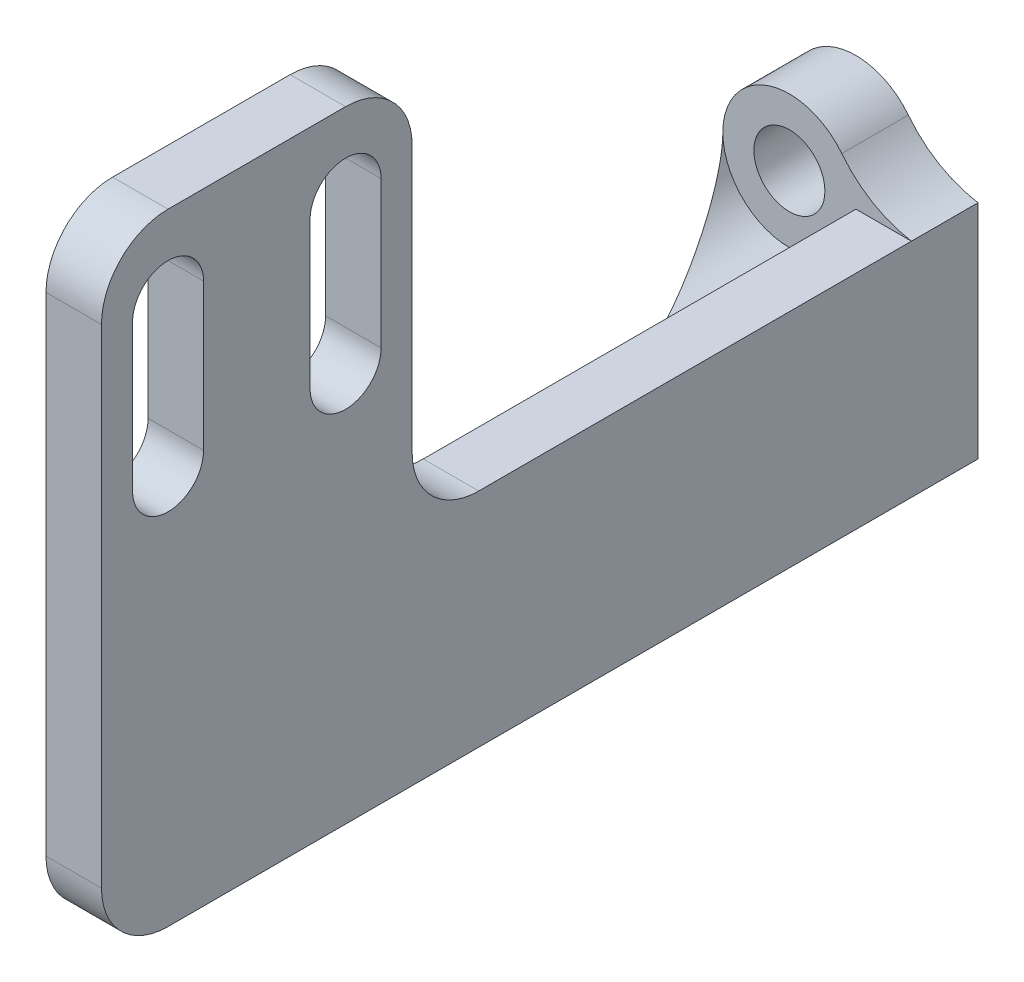
SolidWorks part; units mm, degrees
ref_plane "Front Plane" through (0, 0, 0) normal (0, 0, 1) x (1, 0, 0)
ref_plane "Top Plane" through (0, 0, 0) normal (0, 1, 0) x (1, 0, 0)
ref_plane "Right Plane" through (0, 0, 0) normal (1, 0, 0) x (0, 0, -1)
other "Configuration Table"
sketch "草图1" plane through (0, 0, 0) normal (0, 0, 1) x (1, 0, 0)
  line L0 (-3, -33.0103) -> (-3, -43.0103)
  line L1 (3, -33.0103) -> (3, -43.0103)
  line L3 (3, -33.0103) -> (5.5, -33.0103)
  line L4 (5.5, -33.0103) -> (5.5, -43.0103)
  line L5 (5.5, -43.0103) -> (3, -43.0103)
  circle A0 centre (0, -33.0103) radius 1.6
  circle A1 centre (0, -43.0103) radius 1.6
  circle A2 centre (0, -33.0103) radius 3
  circle A3 centre (0, -43.0103) radius 3
extrude "凸台-拉伸1" add sketch "草图1" along normal blind 3 contours A3 L1 A2 L0 | A2 A0 | A3 A1
sketch "草图2" plane through (0, 0, 3) normal (0, 0, 1) x (1, 0, 0)
  line L0 (0, -41.4103) -> (0, -34.6103) construction
  circle A0 centre (0, -43.0103) radius 1.6 construction
  circle A1 centre (0, -33.0103) radius 1.6 construction
sketch "草图3" plane through (0, 0, 3) normal (0, 0, 1) x (1, 0, 0)
  line L1 (5.5, -43.0103) -> (5.5, -33.0103)
  line L2 (5.5, -33.0103) -> (3, -33.0103)
  line L3 (3, -33.0103) -> (3, -43.0103)
  line L4 (3, -43.0103) -> (5.5, -43.0103)
extrude "凸台-拉伸2" add sketch "草图3" along normal blind 36.5
fillet "圆角1" radius 5 1 edges at (3, -43.0103, 1.5)
fillet "圆角2" radius 5 1 edges at (3, -33.0103, 1.5)
sketch "草图4" plane through (5.5, 0, 0) normal (1, 0, 0) x (0, 0, -1)
  line L1 (-39.5, -38.0103) -> (0, -38.0103) construction
  line L4 (-39.5, -33.0103) -> (-39.5, -15.0103)
  line L7 (-39.5, -43.0103) -> (-39.5, -33.0103) construction
  line L8 (0, -33.0103) -> (0, -43.0103) construction
  line L13 (-39.5, -15.0103) -> (-25.5, -15.0103)
  line L14 (-25.5, -15.0103) -> (-25.5, -33.0103)
  line L15 (-39.5, -33.0103) -> (-25.5, -33.0103)
extrude "凸台-拉伸3" add sketch "草图4" against normal up to surface (2.5 mm away) up to face at (3, -38.0103, 21.25)
sketch "草图5" plane through (5.5, 0, 0) normal (1, 0, 0) x (0, 0, -1)
  line L0 (-36.5, -18.6179) -> (-36.5, -25.2232) construction
  line L1 (-34.9, -18.6179) -> (-34.9, -25.2232)
  line L2 (-38.1, -18.6179) -> (-38.1, -25.2232)
  line L3 (-28.5, -18.6179) -> (-28.5, -25.2232) construction
  line L4 (-30.1, -18.6179) -> (-30.1, -25.2232)
  line L5 (-26.9, -18.6179) -> (-26.9, -25.2232)
  line L8 (-32.5, -15.0103) -> (-36.5, -15.0103) construction
  line L11 (0, -38.0103) -> (-39.5, -38.0103) construction
  line L12 (0, -33.0103) -> (0, -43.0103) construction
  line L13 (-39.5, -43.0103) -> (-39.5, -15.0103) construction
  line L14 (-32.5, -15.0103) -> (-32.5, -38.0103) construction
  line L23 (-36.5, -15.0103) -> (-36.5, -17.0103) construction
  arc A8 (-34.9, -18.6179) -> (-38.1, -18.6179) centre (-36.5, -18.6179) ccw
  arc A9 (-38.1, -25.2232) -> (-34.9, -25.2232) centre (-36.5, -25.2232) ccw
  arc A10 (-30.1, -18.6179) -> (-26.9, -18.6179) centre (-28.5, -18.6179) cw
  arc A11 (-26.9, -25.2232) -> (-30.1, -25.2232) centre (-28.5, -25.2232) cw
  point P2 (-36.5, -21.9206)
  point P10 (-28.5, -21.9206)
extrude "切除-拉伸1" cut sketch "草图5" against normal through all
sketch "草图6" plane through (0, -43.0103, 0) normal (0, -1, 0) x (1, 0, 0)
  line L0 (3, 14) -> (-3, 3)
  line L1 (-3, 3) -> (3, 3)
  line L2 (3, 3) -> (3, 14)
  line L3 (3, 39.5) -> (3, 3) construction
extrude "凸台-拉伸4" add sketch "草图6" against normal up to surface (10 mm away) up to face at (4.25, -33.0103, 14.25)
sketch "草图8" plane through (0, 0, 3) normal (0, 0, 1) x (1, 0, 0)
  line L0 (3, -43.0103) -> (-3, -43.0103) construction
  line L1 (3, -33.0103) -> (-3, -33.0103) construction
  circle A1 centre (0, -43.0103) radius 3
  circle A3 centre (0, -33.0103) radius 3
extrude "切除-拉伸2" cut sketch "草图8" along normal through all
fillet "圆角3" radius 3 4 edges at (4.25, -43.0103, 39.5) (4.25, -33.0103, 25.5) (4.25, -15.0103, 39.5) (4.25, -15.0103, 25.5)
